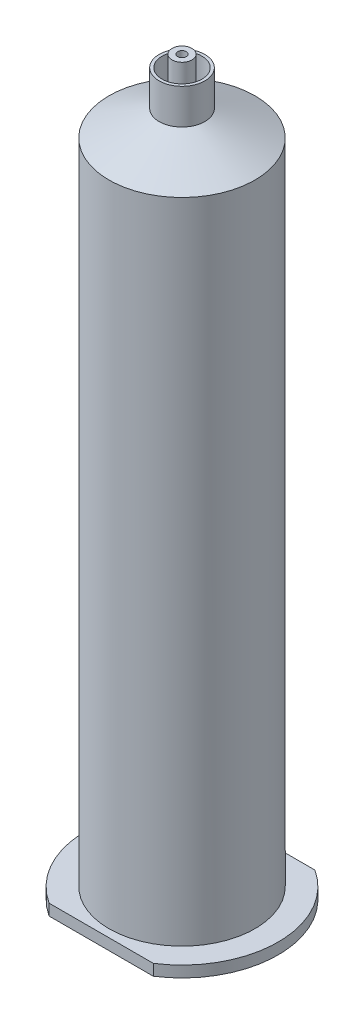
SolidWorks part; units mm, degrees
material "ABS"
ref_plane "Front Plane" through (0, 0, 0) normal (0, 0, 1) x (1, 0, 0)
ref_plane "Top Plane" through (0, 0, 0) normal (0, 1, 0) x (1, 0, 0)
ref_plane "Right Plane" through (0, 0, 0) normal (1, 0, 0) x (0, 0, -1)
sketch "Sketch3" plane through (0, 0, 0) normal (0, 1, 0) x (1, 0, 0)
  line L1 (-16.6, 16.6) -> (16.6, 16.6) construction
  line L2 (-16.6, 16.6) -> (-16.6, -16.6) construction
  line L3 (-16.6, -16.6) -> (16.6, -16.6) construction
  line L4 (16.6, 16.6) -> (16.6, -16.6) construction
  line L5 (-16.6, 16.6) -> (16.6, -16.6) construction
  line L6 (-16.6, -16.6) -> (16.6, 16.6) construction
  line L8 (-10.7006, 16.6) -> (10.7006, 16.6)
  line L9 (0, 0) -> (0, 16.6) construction
  line L26 (-10.7006, -16.6) -> (10.7006, -16.6)
  arc A18 (-10.7006, 16.6) -> (-10.7006, -16.6) centre (0, 0) ccw
  arc A19 (10.7006, -16.6) -> (10.7006, 16.6) centre (0, 0) ccw
  point P0 (0, 0)
  dimension "D1" = 39.5
  dimension "D2" = 33.2
extrude "Boss-Extrude2" add sketch "Sketch3" along normal blind 1.3
sketch "Sketch4" plane through (0, 1.3, 0) normal (0, 1, 0) x (1, 0, 0)
  line L6 (10.7006, 16.6) -> (-10.7006, 16.6)
  line L7 (10.7006, 16.6) -> (-10.7006, 16.6)
  line L8 (-10.7006, -16.6) -> (10.7006, -16.6)
  line L9 (-10.7006, -16.6) -> (10.7006, -16.6)
  arc A6 (10.7006, -16.6) -> (10.7006, 16.6) centre (0, 0) ccw
  arc A7 (10.7006, -16.6) -> (10.7006, 16.6) centre (0, 0) ccw
  arc A8 (-10.7006, 16.6) -> (-10.7006, -16.6) centre (0, 0) ccw
  arc A9 (-10.7006, 16.6) -> (-10.7006, -16.6) centre (0, 0) ccw
  dimension "D1" = 0
extrude "Boss-Extrude3" add sketch "Sketch4" along normal blind 1
sketch "Sketch5" plane through (0, 0, 0) normal (0, -1, 0) x (1, 0, 0)
  circle A0 centre (0, 0) radius 15
  dimension "D1" = 30
extrude "Boss-Extrude4" add sketch "Sketch5" against normal blind 135.5 contours A0
fillet "Fillet1" [suppressed] radius 0.81
sketch "Sketch6" plane through (0, 0, 0) normal (0, -1, 0) x (1, 0, 0)
  circle A0 centre (0, 0) radius 13.75
  dimension "D1" = 27.5
extrude "Cut-Extrude2" cut sketch "Sketch6" against normal through all
sketch "Sketch7" plane through (0, 135.5, 0) normal (0, 1, 0) x (1, 0, 0)
  circle A0 centre (0, 0) radius 13.75 construction
  circle A1 centre (0, 0) radius 13.75
sketch "Sketch8" plane through (0, 135.5, 0) normal (0, 1, 0) x (1, 0, 0)
  circle A0 centre (0, 0) radius 15 construction
  circle A1 centre (0, 0) radius 15
ref_plane "Plane2" through (0, 141.5, 0) normal (0, 1, 0) x (1, 0, 0)
sketch "Sketch9" plane through (0, 141.5, 0) normal (0, 1, 0) x (1, 0, 0)
  circle A0 centre (0, 0) radius 2.05
  dimension "D1" = 4.1
sketch "Sketch10" plane through (0, 141.5, 0) normal (0, 1, 0) x (1, 0, 0)
  circle A0 centre (0, 0) radius 0.9
  dimension "D1" = 1.8
loft "Loft1" add profiles "Sketch9", "Sketch8" connector at (-0.9604, 141.5, 1.8111) connector at (-13.8292, 135.5, 5.8098)
loft "Cut-Loft1" cut profiles "Sketch7", "Sketch10" connector at (0, 135.5, 13.75) connector at (0, 141.5, 0.9)
ref_plane "Plane4" through (0, 140.75, 0) normal (0, 1, 0) x (1, 0, 0)
sketch "Sketch11" plane through (0, 140.75, 0) normal (0, 1, 0) x (1, 0, 0)
  circle A0 centre (0, 0) radius 4.7
  circle A1 centre (0, 0) radius 4.1
  dimension "D1" = 9.4
  dimension "D2" = 0.6
extrude "Boss-Extrude5" add sketch "Sketch11" along normal blind 7.25 separate body
sketch "Sketch12" plane through (0, 141.5, 0) normal (0, 1, 0) x (1, 0, 0)
  circle A0 centre (0, 0) radius 0.9 construction
  circle A1 centre (0, 0) radius 2.05
  circle A2 centre (0, 0) radius 2.05
  circle A3 centre (0, 0) radius 0.9
  dimension "D1" = 0
extrude "Boss-Extrude6" add sketch "Sketch12" along normal offset from surface (8.9 mm away) 2.4 up to face at (0, 148, 4.7) offset beyond the face yes
ref_axis "Axis1" through (0, 135.5, 0) along (0, -1, 0)
